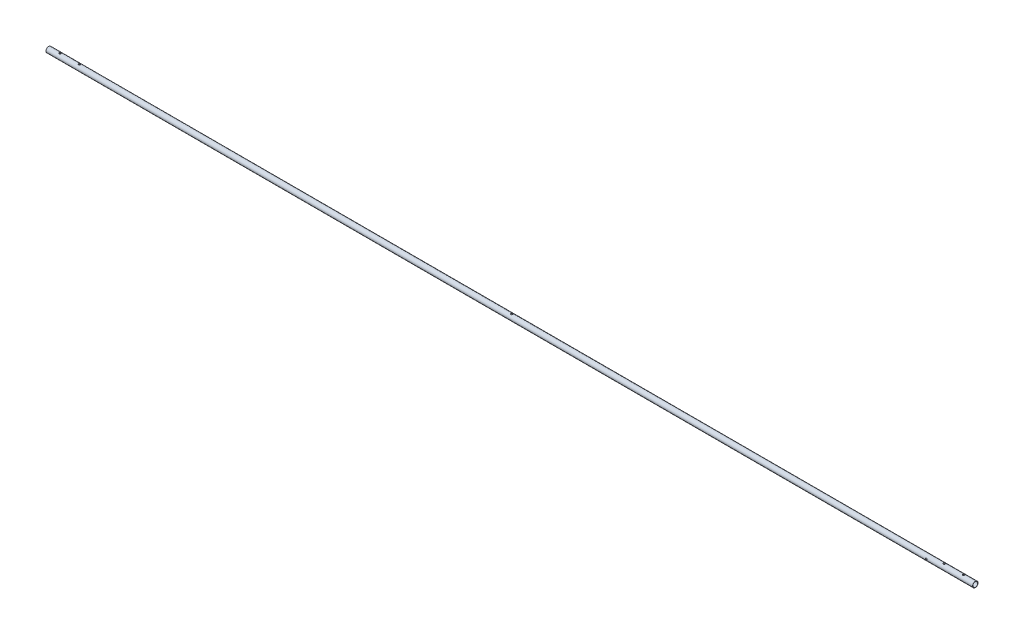
SolidWorks part; units mm, degrees
material "Galvanized Steel"
ref_plane "Front Plane" through (0, 0, 0) normal (0, 0, 1) x (1, 0, 0)
ref_plane "Top Plane" through (0, 0, 0) normal (0, 1, 0) x (1, 0, 0)
ref_plane "Right Plane" through (0, 0, 0) normal (1, 0, 0) x (0, 0, -1)
sketch "Sketch1" plane through (0, 0, 0) normal (1, 0, 0) x (0, 0, -1)
  circle A0 centre (0, 0) radius 7.8994
  circle A1 centre (0, 0) radius 8.9662
  dimension "D1" = 15.7988
  dimension "D2" = 17.9324
extrude "Boss-Extrude1" add sketch "Sketch1" along normal blind 3048
sketch "Sketch2" plane through (0, 0, 0) normal (0, 1, 0) x (1, 0, 0)
  line L0 (0, 8.9662) -> (0, -8.9662) construction
  line L1 (3048, -8.9662) -> (3048, 8.9662) construction
  circle A0 centre (38.1, 0) radius 3.175
  circle A1 centre (3009.9, 0) radius 3.175
  circle A2 centre (101.6, 0) radius 3.175
  circle A3 centre (2946.4, 0) radius 3.175
  dimension "D1" = 6.35
  dimension "D3" = 6.35
  dimension "D5" = 6.35
  dimension "D7" = 6.35
  dimension "D2" = 38.1
  dimension "D4" = 38.1
  dimension "D6" = 101.6
  dimension "D8" = 101.6
sketch "Sketch3" plane through (0, 0, 0) normal (0, 1, 0) x (1, 0, 0)
  line L0 (0, 8.9662) -> (0, -8.9662) construction
  circle A0 centre (1524, 0) radius 3.175
  dimension "D1" = 6.35
  dimension "D2" = 1524
extrude "Cut-Extrude2" cut sketch "Sketch3" against normal through all and the other way through all
extrude "Cut-Extrude5" cut sketch "Sketch2" against normal through all and the other way through all
sketch "Sketch4" plane through (0, 0, 0) normal (0, 0, 1) x (1, 0, 0)
  line L1 (3048, -8.9662) -> (3048, 8.9662) construction
  circle A0 centre (2895.6, 0) radius 3.175
  dimension "D1" = 152.4
extrude "Cut-Extrude6" cut sketch "Sketch4" against normal through all and the other way through all
ref_plane "Plane1" through (0, -6.1186, 6.5541) normal (0, -0.6824, 0.731) x (1, 0, 0)
